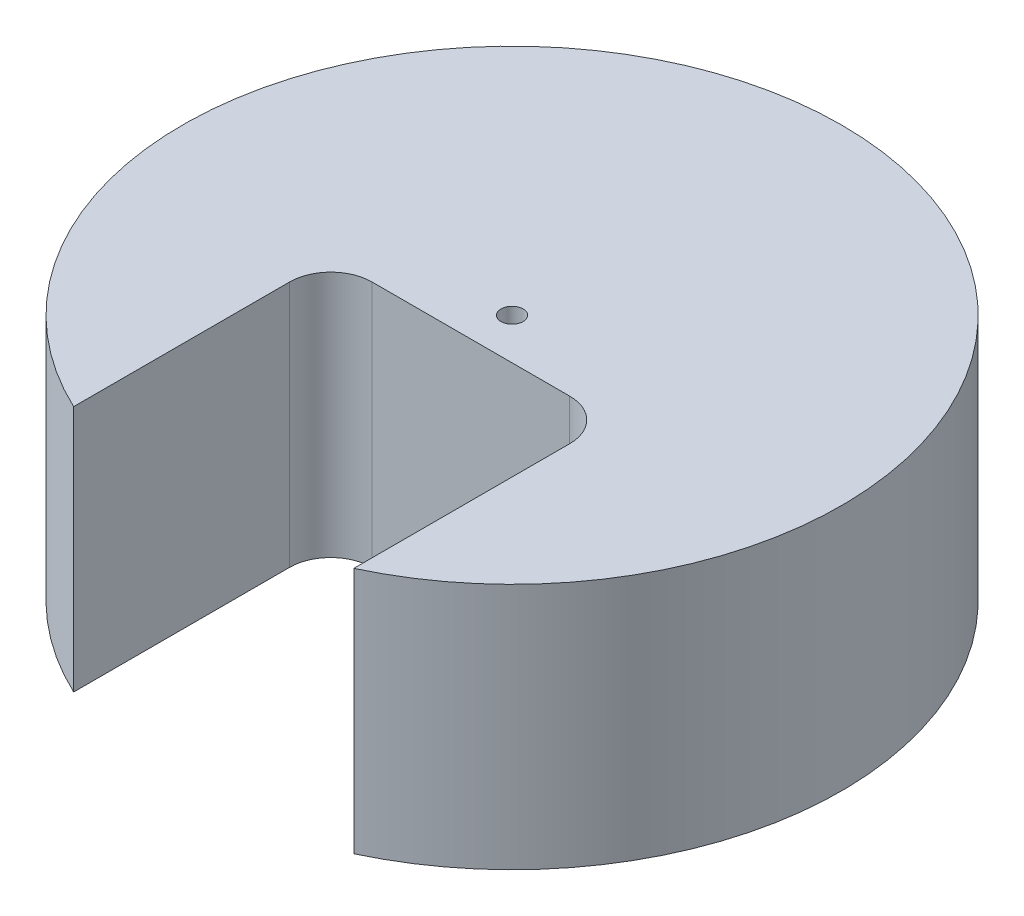
SolidWorks part; units mm, degrees
ref_plane "Front Plane" through (0, 0, 0) normal (0, 0, 1) x (1, 0, 0)
ref_plane "Top Plane" through (0, 0, 0) normal (0, 1, 0) x (1, 0, 0)
ref_plane "Right Plane" through (0, 0, 0) normal (1, 0, 0) x (0, 0, -1)
sketch "Sketch1" plane through (0, 0, 0) normal (0, 1, 0) x (1, 0, 0)
  circle A0 centre (0, 0) radius 50.8
  dimension "D1" = 101.6
extrude "Boss-Extrude1" add sketch "Sketch1" along normal blind 38.1
sketch "Sketch2" plane through (0, 38.1, 0) normal (0, 1, 0) x (1, 0, 0)
  line L1 (-21.59, -6.35) -> (21.59, -6.35)
  line L2 (-21.59, -6.35) -> (-21.59, -50.8)
  line L3 (-21.59, -50.8) -> (21.59, -50.8)
  line L4 (21.59, -6.35) -> (21.59, -50.8)
  circle A1 centre (0, 0) radius 50.8 construction
  point P7 (0, -6.35)
  dimension "D1" = 6.35
  dimension "D2" = 43.18
extrude "Cut-Extrude1" cut sketch "Sketch2" against normal up to next
fillet "Fillet1" radius 6.35 2 edges at (21.59, 19.05, 6.35) (-21.59, 19.05, 6.35)
hole_wizard "M3 Clearance Hole1" positions "Sketch4" profile "Sketch5" hole size "M3" standard "ANSI Metric" end condition through all
sketch "Sketch4" plane through (0, 38.1, 0) normal (0, 1, 0) x (1, 0, 0)
  point P0 (0, 0)
sketch "Sketch5" plane through (0, 38.1, 0) normal (1, 0, 0) x (0, 0, 1)
  line L0 (0, 0) -> (0, 38.1)
  line L1 (0, 38.1) -> (1.7, 38.1)
  line L2 (1.7, 38.1) -> (1.7, 0)
  line L5 (1.7, 0) -> (0, 0)
  line L11 (0, -6.35) -> (0, 107.95) construction
  dimension "Thru Hole Dia." = 3.4
  dimension "Thru Hole Depth" = 38.1
ref_axis "Axis1 - ROTATION AXIS" through (0, 0, 0) along (0, 1, 0)
